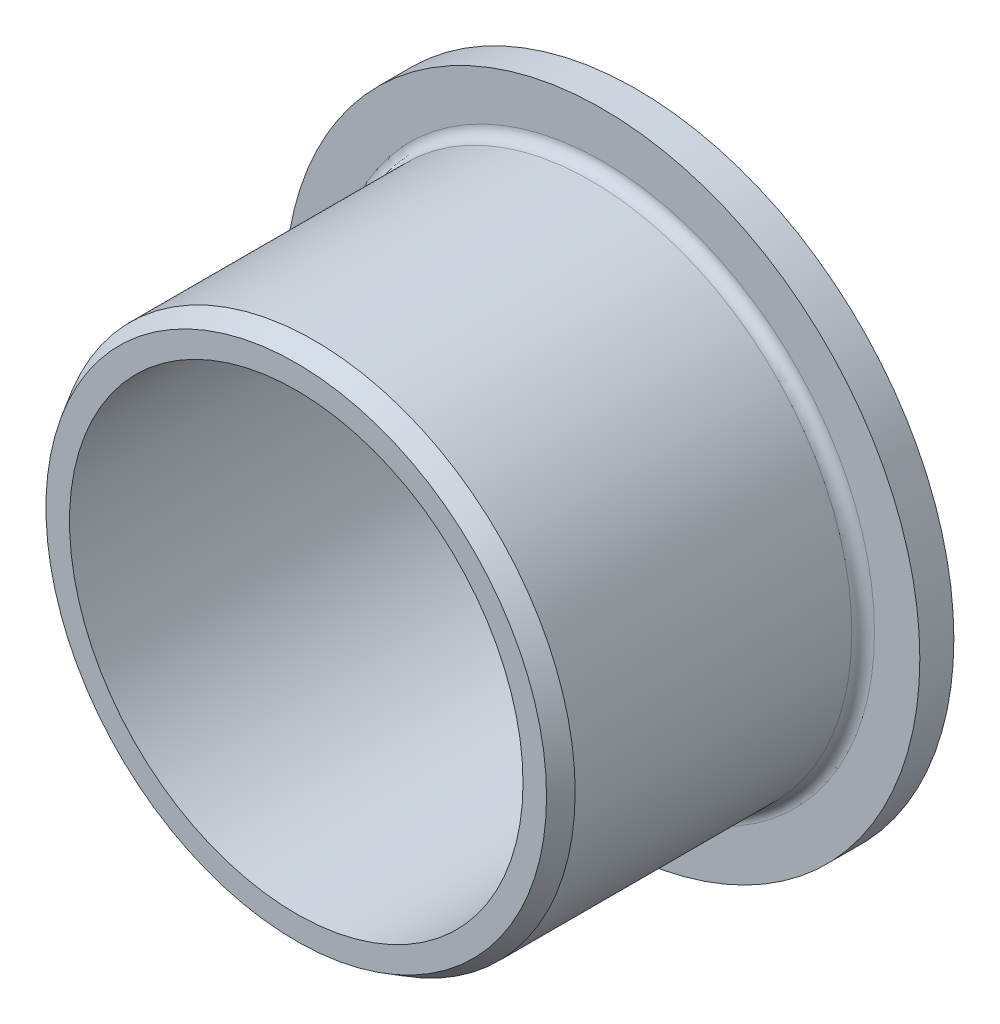
SolidWorks part; units mm, degrees
ref_plane "Płaszczyzna przednia" through (0, 0, 0) normal (0, 0, 1) x (1, 0, 0)
ref_plane "Płaszczyzna górna" through (0, 0, 0) normal (0, 1, 0) x (1, 0, 0)
ref_plane "Płaszczyzna prawa" through (0, 0, 0) normal (1, 0, 0) x (0, 0, -1)
sketch "Szkic1" plane through (0, 0, 0) normal (0, 0, 1) x (1, 0, 0)
  circle A0 centre (0, 0) radius 11.5
  dimension "D1" = 23
extrude "Wyciągnięcie-cienka ścianka1" add sketch "Szkic1" along normal blind 1.5 thin thin type one direction wall 2.5
sketch "Szkic2" plane through (0, 0, 0) normal (0, 0, 1) x (1, 0, 0)
  circle A0 centre (0, 0) radius 10
  circle A1 centre (0, 0) radius 11.5 construction
  circle A2 centre (0, 0) radius 11.5
  dimension "D1" = 20
extrude "Dodanie-wyciągnięcie1" add sketch "Szkic2" along normal blind 15
fillet "Zaokrąglenie1" radius 0.5 1 edges at (11.5, 0, 1.5)
chamfer "Sfazowanie1" distance 0.8 angle 30 1 edges at (11.5, 0, 15) first distance on face at (11.5, 0, 2)
